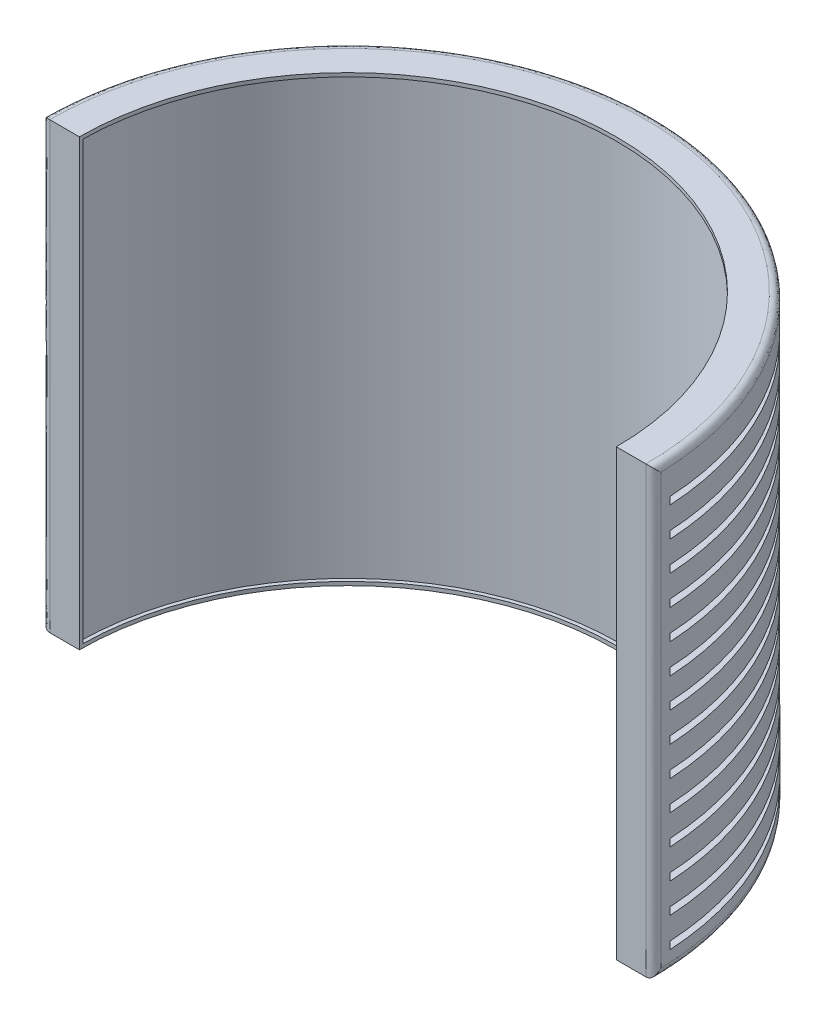
SolidWorks part; units mm, degrees
material "PE High Density Film"
ref_plane "Front Plane" through (0, 0, 0) normal (0, 0, 1) x (1, 0, 0)
ref_plane "Top Plane" through (0, 0, 0) normal (0, 1, 0) x (1, 0, 0)
ref_plane "Right Plane" through (0, 0, 0) normal (1, 0, 0) x (0, 0, -1)
sketch "Sketch1" plane through (0, 0, 0) normal (0, 1, 0) x (1, 0, 0)
  line L0 (-209.55, 0) -> (-184.15, 0)
  line L2 (-182.3899, 25.4) -> (182.3899, 25.4) construction
  line L3 (184.15, 0) -> (209.55, 0)
  line L4 (-209.55, 0) -> (209.55, 0) construction
  arc A0 (209.55, 0) -> (-209.55, 0) centre (0, 0) ccw
  arc A1 (184.15, 0) -> (-184.15, 0) centre (0, 0) ccw
  arc A2 (182.3899, 25.4) -> (-182.3899, 25.4) centre (0, 0) ccw construction
  dimension "D1" = 25.4
  dimension "D2" = 209.55
extrude "Boss-Extrude1" add sketch "Sketch1" against normal blind 304.8
ref_plane "Plane1" through (0, -2.54, 0) normal (0, 1, 0) x (1, 0, 0)
sketch "Sketch5" plane through (0, -2.54, 0) normal (0, 1, 0) x (1, 0, 0)
  line L3 (-184.1325, 2.54) -> (-186.6727, 2.54)
  line L5 (184.1325, 2.54) -> (186.6727, 2.54)
  arc A0 (184.1325, 2.54) -> (-184.1325, 2.54) centre (0, 0) ccw
  arc A1 (186.6727, 2.54) -> (-186.6727, 2.54) centre (0, 0) ccw
  arc A2 (184.15, 0) -> (-184.15, 0) centre (0, 0) ccw construction
  arc A3 (186.69, 0) -> (-186.69, 0) centre (0, 0) ccw construction
  dimension "D2" = 184.15
  dimension "D3" = 184.1325
  dimension "D1" = 2.54
extrude "Cut-Extrude1" cut sketch "Sketch5" against normal blind 299.72
ref_plane "Plane2" through (0, -22.86, 0) normal (0, 1, 0) x (1, 0, 0)
sketch "Sketch9" plane through (0, -22.86, 0) normal (0, 1, 0) x (1, 0, 0)
  line L1 (-134.84, 150.3127) -> (-140.2853, 155.6638)
  line L2 (-8.111, 201.767) -> (-8.1776, 209.3904)
  line L3 (9.1809, 201.7212) -> (9.0476, 209.3546)
  line L4 (135.6352, 149.5955) -> (140.931, 155.0795)
  line L5 (147.9365, 137.4428) -> (153.1918, 142.9807)
  line L6 (201.5947, 11.6311) -> (209.2158, 11.8307)
  line L16 (-201.5302, 12.7) -> (-209.1648, 12.7)
  line L25 (-147.2056, 138.2253) -> (-152.5963, 143.6161)
  line L26 (201.8507, -5.659) -> (209.4806, -5.3925)
  line L27 (151.9399, -133.0037) -> (157.5155, -138.203)
  arc A2 (-152.5963, 143.6161) -> (-209.1648, 12.7) centre (0, 0) ccw
  arc A3 (-8.111, 201.767) -> (-134.84, 150.3127) centre (0, 0) ccw
  arc A4 (-147.2056, 138.2253) -> (-201.5302, 12.7) centre (0, 0) ccw
  arc A5 (-8.1776, 209.3904) -> (-140.2853, 155.6638) centre (0, 0) ccw
  arc A6 (135.6352, 149.5955) -> (9.1809, 201.7212) centre (0, 0) ccw
  arc A7 (140.931, 155.0795) -> (9.0476, 209.3546) centre (0, 0) ccw
  arc A8 (201.5947, 11.6311) -> (147.9365, 137.4428) centre (0, 0) ccw
  arc A9 (209.2158, 11.8307) -> (153.1918, 142.9807) centre (0, 0) ccw
  arc A12 (151.9399, -133.0037) -> (201.8507, -5.659) centre (0, 0) ccw
  arc A13 (157.5155, -138.203) -> (209.4806, -5.3925) centre (0, 0) ccw
  dimension "D2" = 201.93
  dimension "D3" = 147.2056
  dimension "D1" = 209.55
  dimension "D4" = 152.5963
  dimension "D5" = 201.5302
  dimension "D6" = 9.0476
  dimension "D8" = 5
extrude "Cut-Extrude2" cut sketch "Sketch9" against normal blind 5.08
pattern_linear "LPattern1" count 10 spacing 20.32 along (0, -1, 0) count 10 spacing 20.32 along (0, -1, 0) of "Cut-Extrude2"
fillet "Fillet1" radius 5.08 4 edges at (-209.55, -152.4, 0) (209.55, -152.4, 0) (0, -304.8, -209.55) (0, 0, -209.55)
hole_wizard "#8 (0.25) Diameter Hole1" positions "3DSketch3" profile "Sketch11" hole size "#8" standard "ANSI Inch"
sketch3d "3DSketch3"
  line L0 (9.0476, -231.14, -209.3546) -> (9.0476, -226.06, -209.3546) construction
  line L1 (9.0476, -271.78, -209.3546) -> (9.0476, -266.7, -209.3546) construction
  line L4 (14.8722, -299.72, -209.0216) -> (-14.8722, -299.72, -209.0216) construction
  arc A4 (209.4853, -299.72, -5.2062) -> (-209.4853, -299.72, -5.2062) centre (0, -299.72, 0) ccw construction
  point P0 (0.4138, -292.1296, -209.5496)
  point P2 (0.4138, -254.0296, -209.5496)
  point P34 (0, -90.17, 0)
  point P36 (0, -299.72, -209.0216)
  dimension "D3" = 38.1
  dimension "D1" = 8.636
  dimension "D2" = 8.636
  dimension "D4" = 7.62
sketch "Sketch11" plane through (0.4138, -292.1296, -209.5496) normal (0, 1, 0) x (-1, 0, -0.002)
  line L0 (0, 0) -> (0, 16.6397)
  line L1 (0, 16.6397) -> (3.175, 14.732)
  line L2 (3.175, 14.732) -> (3.175, 0)
  line L5 (3.175, 0) -> (0, 0)
  line L10 (0, 16.6397) -> (-3.175, 14.732) construction
  line L11 (0, -6.35) -> (0, 107.95) construction
  dimension "Hole Dia." = 6.35
  dimension "Hole Depth" = 14.732
  dimension "Drill Angle" = 118
